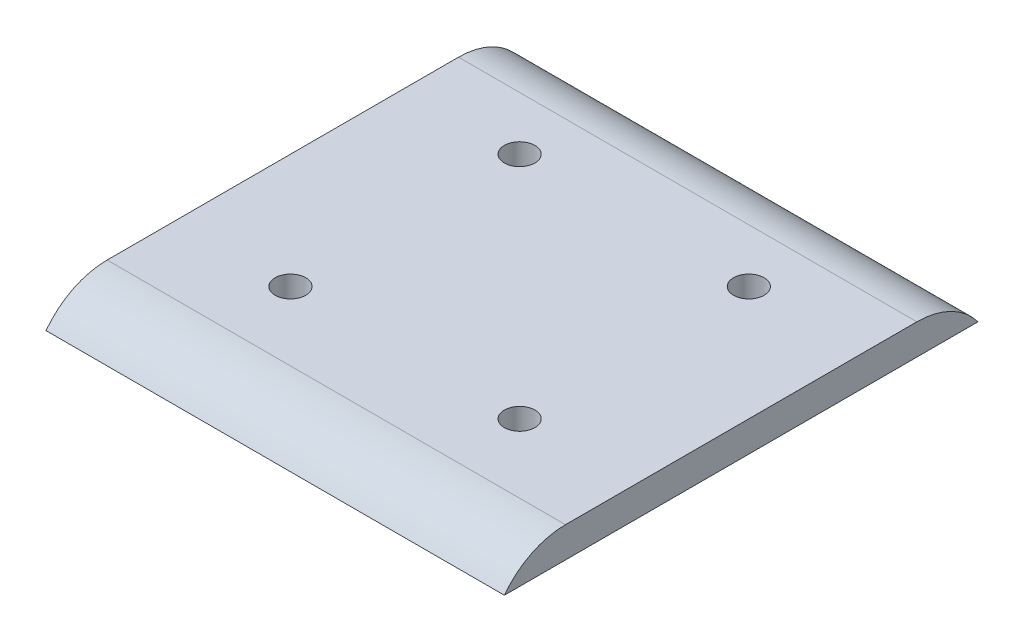
SolidWorks part; units mm, degrees
ref_plane "Front Plane" through (0, 0, 0) normal (0, 0, 1) x (1, 0, 0)
ref_plane "Top Plane" through (0, 0, 0) normal (0, 1, 0) x (1, 0, 0)
ref_plane "Right Plane" through (0, 0, 0) normal (1, 0, 0) x (0, 0, -1)
sketch "Sketch1" plane through (0, 0, 0) normal (0, 1, 0) x (1, 0, 0)
  line L1 (-17.3267, 10.9901) -> (12.6733, 10.9901)
  line L2 (-17.3267, 10.9901) -> (-17.3267, -20.0099)
  line L3 (-17.3267, -20.0099) -> (12.6733, -20.0099)
  line L4 (12.6733, 10.9901) -> (12.6733, -20.0099)
  dimension "D1" = 30
  dimension "D2" = 31
extrude "Boss-Extrude1" add sketch "Sketch1" along normal blind 2
sketch "Sketch2" plane through (0, 0, 0) normal (0, 1, 0) x (1, 0, 0)
  line L0 (12.6733, 10.9901) -> (-17.3267, 10.9901) construction
  line L1 (-17.3267, 10.9901) -> (-17.3267, -20.0099) construction
  line L2 (12.6733, -20.0099) -> (12.6733, 10.9901) construction
  circle A0 centre (-9.8267, 3.4901) radius 1
  circle A1 centre (-9.8267, -11.5099) radius 1
  circle A2 centre (5.1733, 3.4901) radius 1
  circle A3 centre (5.1733, -11.5099) radius 1
  dimension "D1" = 7.5
  dimension "D3" = 15
  dimension "D5" = 15
  dimension "D2" = 7.5
  dimension "D4" = 7.5
  dimension "D6" = 15
  dimension "D7" = 7.5
  dimension "D8" = 15
  dimension "D9" = 7.5
extrude "Cut-Extrude2" cut sketch "Sketch2" along normal blind 4
fillet "Fillet2" radius 5 1 edges at (-2.3267, 2, 20.0099)
fillet "Fillet3" radius 5 1 edges at (-2.3267, 2, -10.9901)
